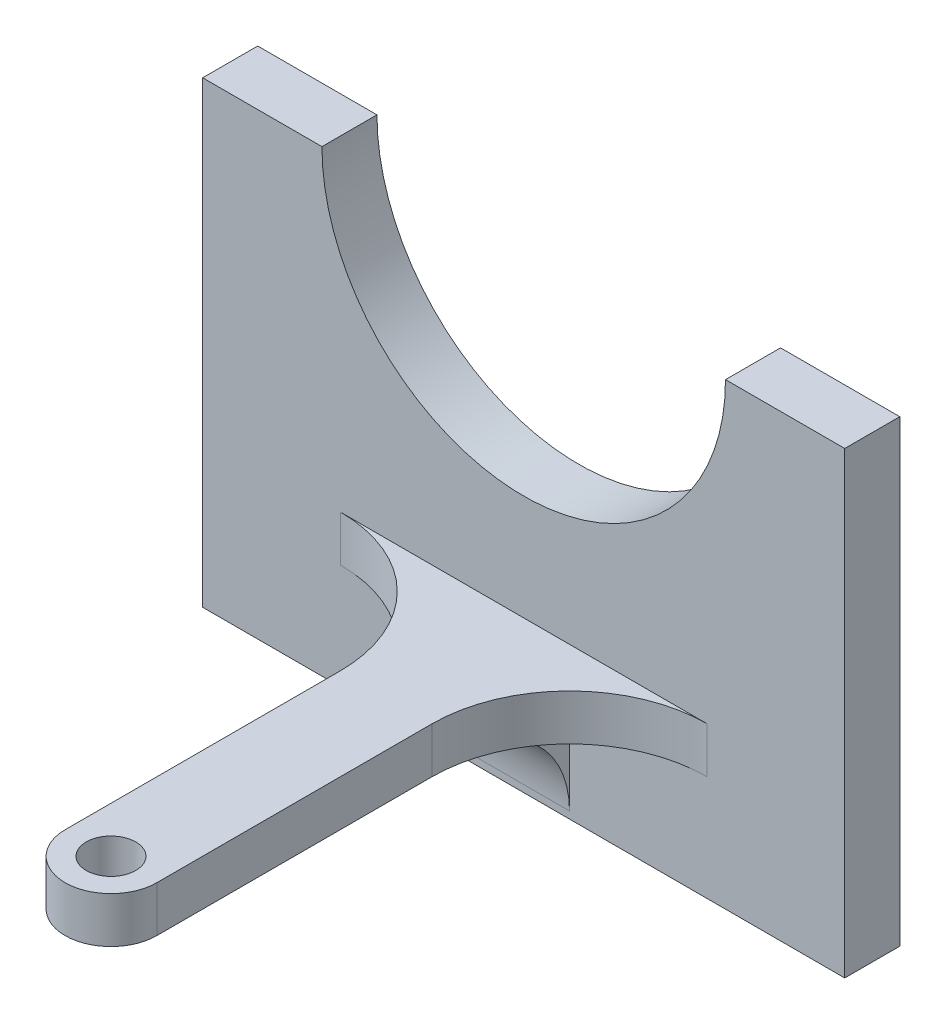
SolidWorks part; units mm, degrees
ref_plane "Front Plane" through (0, 0, 0) normal (0, 0, 1) x (1, 0, 0)
ref_plane "Top Plane" through (0, 0, 0) normal (0, 1, 0) x (1, 0, 0)
ref_plane "Right Plane" through (0, 0, 0) normal (1, 0, 0) x (0, 0, -1)
sketch "Sketch1" plane through (0, 0, 0) normal (0, 0, 1) x (1, 0, 0)
  line L1 (35, -25) -> (-35, -25)
  line L2 (35, -25) -> (35, 25)
  line L3 (35, 25) -> (-35, 25)
  line L4 (-35, -25) -> (-35, 25)
  line L5 (35, -25) -> (-35, 25) construction
  line L6 (35, 25) -> (-35, -25) construction
  arc A0 (-22, 25) -> (22, 25) centre (0, 25) ccw
  point P0 (0, 0)
extrude "Boss-Extrude1" add sketch "Sketch1" along normal blind 4 and the other way blind 2 contours A0 L3 L4 L1 L2 region at (0, -4.3464, 0)
sketch "Sketch2" plane through (0, 0, 4) normal (0, 0, 1) x (1, 0, 0)
  line L0 (0, -25) -> (0, 3) construction
  line L1 (35, -25) -> (-35, -25) construction
  line L3 (5, -8.5) -> (-5, -8.5)
  line L4 (5, -8.5) -> (5, -13.5)
  line L5 (5, -13.5) -> (-5, -13.5)
  line L6 (-5, -8.5) -> (-5, -13.5)
  line L7 (5, -8.5) -> (-5, -13.5) construction
  line L8 (5, -13.5) -> (-5, -8.5) construction
  arc A0 (-22, 25) -> (22, 25) centre (0, 25) ccw construction
  point P7 (0, -11)
extrude "Boss-Extrude2" add sketch "Sketch2" along normal blind 50
fillet "Fillet1" 2 edges at (5, -11, 54) (-5, -11, 54) type full round first side face at (5, -11, 29) second side face at (-5, -11, 29) middle face at (0, -11, 54)
sketch "Sketch3" plane through (0, -8.5, 0) normal (0, 1, 0) x (1, 0, 0)
  line L0 (-5, -49) -> (5, -49) construction
  circle A0 centre (0, -49) radius 2.7
extrude "Cut-Extrude1" cut sketch "Sketch3" against normal blind 35
sketch "Sketch6" plane through (0, -13.5, 0) normal (0, -1, 0) x (1, 0, 0)
  line L0 (5, 4) -> (20, 4)
  line L1 (22, 4) -> (-22, 4) construction
  line L2 (5, 4) -> (5, 19)
  line L3 (5, 49) -> (5, 4) construction
  line L4 (-5, 4) -> (-20, 4)
  line L5 (-5, 4) -> (-5, 19)
  line L6 (-5, 49) -> (-5, 4) construction
  arc A0 (20, 4) -> (5, 19) centre (20, 19) cw
  arc A1 (-20, 4) -> (-5, 19) centre (-20, 19) ccw
extrude "Boss-Extrude3" add sketch "Sketch6" against normal blind 5
sketch "Sketch9" plane through (0, 0, 0) normal (1, 0, 0) x (0, 0, -1)
  line L3 (-13.1902, -13.5) -> (-4, -13.5)
  line L4 (-4, -13.5) -> (-4, -24.4667)
  arc A0 (-4, -24.4667) -> (-13.1902, -13.5) centre (-14.9994, -24.3502) ccw
  point P4 (0, 0)
  point P11 (-4, -13.5)
  dimension "D1" = 11
extrude "Boss-Extrude5" add sketch "Sketch9" along normal blind 5 and the other way blind 5 contours A0 L4 L3 | L3 L4 A0 region at (0, -15.9492, 6.3105)
